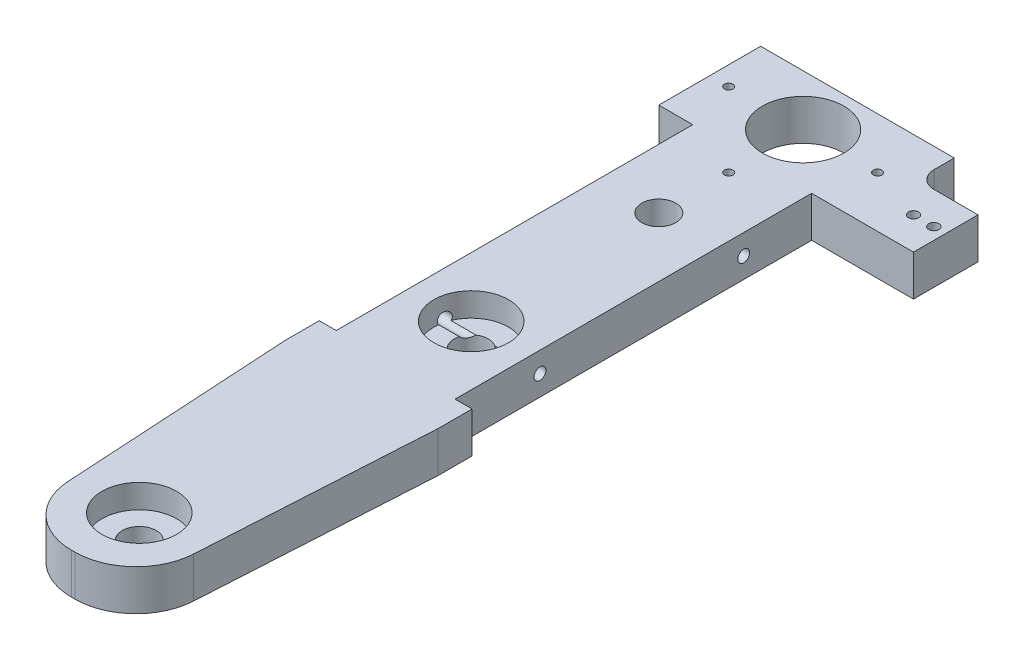
SolidWorks part; units mm, degrees
ref_plane "Front Plane" through (0, 0, 0) normal (0, 0, 1) x (1, 0, 0)
ref_plane "Top Plane" through (0, 0, 0) normal (0, 1, 0) x (1, 0, 0)
ref_plane "Right Plane" through (0, 0, 0) normal (1, 0, 0) x (0, 0, -1)
sketch "Sketch1" plane through (0, 0, 0) normal (0, 1, 0) x (1, 0, 0)
  line L1 (-22.5, 125) -> (22.5, 125)
  line L2 (-22.5, 125) -> (-22.5, -125)
  line L3 (-22.5, -125) -> (22.5, -125)
  line L4 (22.5, 125) -> (22.5, -125)
  line L5 (-22.5, 125) -> (22.5, -125) construction
  line L6 (-22.5, -125) -> (22.5, 125) construction
  point P0 (0, 0)
  dimension "D1" = 250
  dimension "D2" = 45
extrude "Boss-Extrude1" add sketch "Sketch1" along normal blind 12
sketch "Sketch2" plane through (0, 12, 0) normal (0, 1, 0) x (1, 0, 0)
  line L0 (22.5, 125) -> (22.5, 95) construction
  line L1 (22.5, -125) -> (22.5, 125) construction
  line L2 (0, -6.6) -> (0, 6.6) construction
  line L3 (22.5, 95) -> (17.5, 95)
  line L4 (22.5, 95) -> (22.5, -10)
  line L5 (22.5, -10) -> (17.5, -10)
  line L6 (17.5, 95) -> (17.5, -10)
  line L7 (-22.5, -10) -> (-17.5, -10)
  line L8 (-17.5, 95) -> (-17.5, -10)
  line L9 (-22.5, 95) -> (-17.5, 95)
  line L10 (-22.5, 95) -> (-22.5, -10)
  dimension "D2" = 105
  dimension "D1" = 30
  dimension "D3" = 5
extrude "Cut-Extrude1" cut sketch "Sketch2" against normal blind 12
sketch "Sketch3" plane through (17.5, 0, 0) normal (1, 0, 0) x (0, 0, -1)
  line L0 (95, 6) -> (75, 6) construction
  line L1 (95, 0) -> (95, 12) construction
  line L2 (75, 6) -> (15, 6) construction
  circle A0 centre (15, 6) radius 1.75
  circle A1 centre (75, 6) radius 1.75
  dimension "D3" = 3.5
  dimension "D4" = 3.5
  dimension "D1" = 20
  dimension "D2" = 60
extrude "Cut-Extrude2" cut sketch "Sketch3" against normal blind 35
sketch "Sketch5" plane through (0, 12, 0) normal (0, 1, 0) x (1, 0, 0)
  line L1 (22.5, 125) -> (47.5, 125)
  line L2 (22.5, 125) -> (22.5, 95)
  line L3 (22.5, 95) -> (47.5, 95)
  line L4 (47.5, 125) -> (47.5, 95)
  line L5 (-22.5, 125) -> (-27.5, 125)
  line L6 (-22.5, 125) -> (-22.5, 95)
  line L7 (-22.5, 95) -> (-27.5, 95)
  line L8 (-27.5, 125) -> (-27.5, 95)
  dimension "D1" = 30
  dimension "D2" = 25
  dimension "D3" = 30
  dimension "D4" = 5
extrude "Boss-Extrude2" add sketch "Sketch5" against normal up to surface (12 mm away) up to face at (0, 0, -28.3333)
sketch "Sketch7" plane through (0, 12, 0) normal (0, 1, 0) x (1, 0, 0)
  line L0 (0, 125) -> (0, 110) construction
  line L1 (-27.5, 125) -> (0, 125) construction
  line L2 (47.5, 125) -> (-27.5, 125) construction
  line L3 (0, 88.0797) -> (21.9203, 110) construction
  line L4 (21.9203, 110) -> (0, 131.9203) construction
  line L5 (0, 131.9203) -> (-21.9203, 110) construction
  line L6 (-21.9203, 110) -> (0, 88.0797) construction
  circle A0 centre (0, 110) radius 12
  circle A1 centre (0, 110) radius 15.5 construction
  circle A2 centre (21.9203, 110) radius 1.25
  circle A3 centre (-21.9203, 110) radius 1.25
  circle A4 centre (0, 88.0797) radius 1.25
  dimension "D2" = 24
  dimension "D3" = 2.5
  dimension "D4" = 2.5
  dimension "D5" = 2.5
  dimension "D1" = 15
extrude "Cut-Extrude3" cut sketch "Sketch7" against normal blind 35
sketch "Sketch8" plane through (0, 12, 0) normal (0, 1, 0) x (1, 0, 0)
  line L5 (47.5, 125) -> (29.5, 125)
  line L6 (47.5, 125) -> (47.5, 114)
  line L7 (47.5, 114) -> (29.5, 114)
  line L8 (29.5, 125) -> (29.5, 114)
  dimension "D1" = 11
  dimension "D2" = 18
extrude "Cut-Extrude4" cut sketch "Sketch8" against normal blind 12
sketch "Sketch10" plane through (0, 12, 0) normal (0, 1, 0) x (1, 0, 0)
  line L0 (0, 110) -> (0, 30.5) construction
  line L2 (0, -6) -> (0, 30.5) construction
  line L3 (0, -6) -> (0, -85.5) construction
  circle A2 centre (0, 12.25) radius 11
  circle A4 centre (0, -85.5) radius 11
  dimension "D5" = 22
  dimension "D8" = 22
  dimension "D1" = 79.5
  dimension "D3" = 36.5
  dimension "D6" = 79.5
extrude "Cut-Extrude5" cut sketch "Sketch10" against normal blind 7
sketch "Sketch11" plane through (0, 12, 0) normal (0, 1, 0) x (1, 0, 0)
  line L0 (22.5, -125) -> (22.5, -10) construction
  line L4 (-22.5, -125) -> (22.5, -125)
  line L6 (-22.5, -125) -> (-22.5, -105)
  line L12 (-22.5, -105) -> (22.5, -105)
  line L18 (22.5, -125) -> (22.5, -105)
  dimension "D1" = 20
extrude "Cut-Extrude6" cut sketch "Sketch11" against normal blind 20
fillet "Fillet3" radius 5 1 edges at (29.5, 6, -114)
sketch "Sketch12" plane through (0, 5, 0) normal (0, 1, 0) x (1, 0, 0)
  circle A0 centre (0, -85.5) radius 5
  circle A1 centre (0, 12.25) radius 5
  dimension "D1" = 10
  dimension "D2" = 10
extrude "Cut-Extrude7" cut sketch "Sketch12" against normal blind 10
sketch "Sketch13" plane through (0, 12, 0) normal (0, 1, 0) x (1, 0, 0)
  line L0 (47.5, 114) -> (41, 114) construction
  line L1 (34.5, 114) -> (47.5, 114) construction
  line L2 (41, 114) -> (41, 104.5) construction
  line L3 (41, 104.5) -> (38, 104.5) construction
  circle A0 centre (38, 104.5) radius 1.5
  circle A1 centre (44, 104.5) radius 1.5
  dimension "D3" = 3
  dimension "D1" = 9.5
  dimension "D2" = 3
extrude "Cut-Extrude8" cut sketch "Sketch13" against normal up to surface (12 mm away) up to face at (0, 0, 90.5)
sketch "Sketch14" plane through (0, 12, 0) normal (0, 1, 0) x (1, 0, 0)
  line L0 (-22.5, -10) -> (-22.5, -20) construction
  line L1 (-22.5, -10) -> (-22.5, -105) construction
  line L2 (-22.5, -20) -> (-22.5, -105)
  line L3 (-22.5, -105) -> (-17.5, -105)
  line L4 (22.5, -105) -> (-22.5, -105) construction
  line L5 (-17.5, -105) -> (-22.5, -20)
  line L6 (0, -6.6) -> (0, 6.6) construction
  line L7 (17.5, -105) -> (22.5, -20)
  line L8 (22.5, -105) -> (17.5, -105)
  line L9 (22.5, -20) -> (22.5, -105)
  dimension "D1" = 10
  dimension "D2" = 5
extrude "Cut-Extrude9" cut sketch "Sketch14" against normal blind 20
fillet "Fillet4" radius 18 2 edges at (-17.5, 6, 105) (17.5, 6, 105)
sketch "Sketch15" plane through (0, 12, 0) normal (0, 1, 0) x (1, 0, 0)
  line L0 (17.5, 95) -> (0, 95) construction
  line L1 (0, 95) -> (0, 67.5) construction
  circle A0 centre (0, 67.5) radius 5
  dimension "D2" = 10
  dimension "D1" = 27.5
extrude "Cut-Extrude10" cut sketch "Sketch15" against normal blind 10
